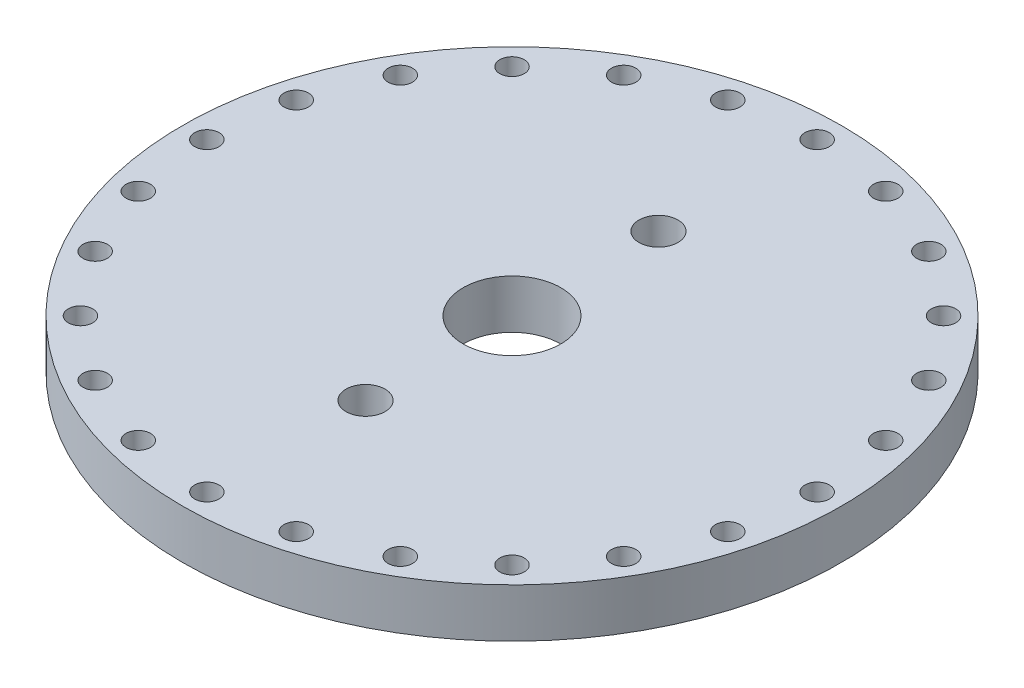
SolidWorks part; units mm, degrees
material "Brass"
ref_plane "Front Plane" through (0, 0, 0) normal (0, 0, 1) x (1, 0, 0)
ref_plane "Top Plane" through (0, 0, 0) normal (0, 1, 0) x (1, 0, 0)
ref_plane "Right Plane" through (0, 0, 0) normal (1, 0, 0) x (0, 0, -1)
sketch "Sketch5" plane through (0, 0, 0) normal (0, 1, 0) x (1, 0, 0)
  line L0 (87.3464, 51.4964) -> (89.0397, 50.8872)
  line L1 (89.0397, 50.8872) -> (90.7249, 50.062)
  line L2 (90.7249, 50.062) -> (90.7249, 49.095)
  line L3 (90.7249, 49.095) -> (89.0397, 48.2698)
  line L4 (89.0397, 48.2698) -> (87.3464, 47.6606)
  line L5 (87.3464, 47.6606) -> (87.2693, 46.4828)
  line L6 (87.2693, 46.4828) -> (88.8685, 45.6578)
  line L7 (88.8685, 45.6578) -> (90.4317, 44.6196)
  line L8 (90.4317, 44.6196) -> (90.3054, 43.6609)
  line L9 (90.3054, 43.6609) -> (88.5268, 43.0627)
  line L10 (88.5268, 43.0627) -> (86.7686, 42.6797)
  line L11 (86.7686, 42.6797) -> (86.5383, 41.5221)
  line L12 (86.5383, 41.5221) -> (88.0162, 40.4955)
  line L13 (88.0162, 40.4955) -> (89.4304, 39.2621)
  line L14 (89.4304, 39.2621) -> (89.1801, 38.328)
  line L15 (89.1801, 38.328) -> (87.3386, 37.9672)
  line L16 (87.3386, 37.9672) -> (85.5454, 37.8169)
  line L17 (85.5454, 37.8169) -> (85.1661, 36.6994)
  line L18 (85.1661, 36.6994) -> (86.4974, 35.4884)
  line L19 (86.4974, 35.4884) -> (87.7385, 34.0811)
  line L20 (87.7385, 34.0811) -> (87.3685, 33.1877)
  line L21 (87.3685, 33.1877) -> (85.4956, 33.0702)
  line L22 (85.4956, 33.0702) -> (83.6981, 33.1553)
  line L23 (83.6981, 33.1553) -> (83.1762, 32.0968)
  line L24 (83.1762, 32.0968) -> (84.3379, 30.7226)
  line L25 (84.3379, 30.7226) -> (85.3848, 29.1653)
  line L26 (85.3848, 29.1653) -> (84.9013, 28.3278)
  line L27 (84.9013, 28.3278) -> (83.0292, 28.4557)
  line L28 (83.0292, 28.4557) -> (81.2581, 28.7747)
  line L29 (81.2581, 28.7747) -> (80.6024, 27.7935)
  line L30 (80.6024, 27.7935) -> (81.575, 26.2794)
  line L31 (81.575, 26.2794) -> (82.4096, 24.5987)
  line L32 (82.4096, 24.5987) -> (81.821, 23.8315)
  line L33 (81.821, 23.8315) -> (79.9815, 24.2028)
  line L34 (79.9815, 24.2028) -> (78.2673, 24.7502)
  line L35 (78.2673, 24.7502) -> (77.4891, 23.8628)
  line L36 (77.4891, 23.8628) -> (78.2556, 22.2348)
  line L37 (78.2556, 22.2348) -> (78.8638, 20.4595)
  line L38 (78.8638, 20.4595) -> (78.18, 19.7757)
  line L39 (78.18, 19.7757) -> (76.4047, 20.3839)
  line L40 (76.4047, 20.3839) -> (74.7767, 21.1504)
  line L41 (74.7767, 21.1504) -> (73.8893, 20.3722)
  line L42 (73.8893, 20.3722) -> (74.4368, 18.658)
  line L43 (74.4368, 18.658) -> (74.808, 16.8186)
  line L44 (74.808, 16.8186) -> (74.0408, 16.2299)
  line L45 (74.0408, 16.2299) -> (72.3602, 17.0645)
  line L46 (72.3602, 17.0645) -> (70.846, 18.0371)
  line L47 (70.846, 18.0371) -> (69.8648, 17.3814)
  line L48 (69.8648, 17.3814) -> (70.1838, 15.6104)
  line L49 (70.1838, 15.6104) -> (70.3117, 13.7382)
  line L50 (70.3117, 13.7382) -> (69.4742, 13.2547)
  line L51 (69.4742, 13.2547) -> (67.9169, 14.3016)
  line L52 (67.9169, 14.3016) -> (66.5427, 15.4634)
  line L53 (66.5427, 15.4634) -> (65.4842, 14.9415)
  line L54 (65.4842, 14.9415) -> (65.5693, 13.1439)
  line L55 (65.5693, 13.1439) -> (65.4518, 11.271)
  line L56 (65.4518, 11.271) -> (64.5584, 10.901)
  line L57 (64.5584, 10.901) -> (63.1511, 12.1422)
  line L58 (63.1511, 12.1422) -> (61.9401, 13.4734)
  line L59 (61.9401, 13.4734) -> (60.8226, 13.0941)
  line L60 (60.8226, 13.0941) -> (60.6724, 11.3009)
  line L61 (60.6724, 11.3009) -> (60.3115, 9.4594)
  line L62 (60.3115, 9.4594) -> (59.3774, 9.2091)
  line L63 (59.3774, 9.2091) -> (58.144, 10.6233)
  line L64 (58.144, 10.6233) -> (57.1174, 12.1012)
  line L65 (57.1174, 12.1012) -> (55.9598, 11.8709)
  line L66 (55.9598, 11.8709) -> (55.5768, 10.1127)
  line L67 (55.5768, 10.1127) -> (54.9786, 8.3341)
  line L68 (54.9786, 8.3341) -> (54.0199, 8.2078)
  line L69 (54.0199, 8.2078) -> (52.9817, 9.771)
  line L70 (52.9817, 9.771) -> (52.1567, 11.3702)
  line L71 (52.1567, 11.3702) -> (50.979, 11.2931)
  line L72 (50.979, 11.2931) -> (50.3698, 9.5998)
  line L73 (50.3698, 9.5998) -> (49.5446, 7.9146)
  line L74 (49.5446, 7.9146) -> (48.5775, 7.9146)
  line L75 (48.5775, 7.9146) -> (47.7523, 9.5998)
  line L76 (47.7523, 9.5998) -> (47.1431, 11.2931)
  line L77 (47.1431, 11.2931) -> (45.9654, 11.3702)
  line L78 (45.9654, 11.3702) -> (45.1403, 9.771)
  line L79 (45.1403, 9.771) -> (44.1021, 8.2078)
  line L80 (44.1021, 8.2078) -> (43.1434, 8.3341)
  line L81 (43.1434, 8.3341) -> (42.5452, 10.1127)
  line L82 (42.5452, 10.1127) -> (42.1622, 11.8709)
  line L83 (42.1622, 11.8709) -> (41.0046, 12.1012)
  line L84 (41.0046, 12.1012) -> (39.978, 10.6233)
  line L85 (39.978, 10.6233) -> (38.7447, 9.2091)
  line L86 (38.7447, 9.2091) -> (37.8106, 9.4594)
  line L87 (37.8106, 9.4594) -> (37.4497, 11.3009)
  line L88 (37.4497, 11.3009) -> (37.2994, 13.0941)
  line L89 (37.2994, 13.0941) -> (36.1819, 13.4734)
  line L90 (36.1819, 13.4734) -> (34.9709, 12.1422)
  line L91 (34.9709, 12.1422) -> (33.5636, 10.901)
  line L92 (33.5636, 10.901) -> (32.6702, 11.271)
  line L93 (32.6702, 11.271) -> (32.5527, 13.1439)
  line L94 (32.5527, 13.1439) -> (32.6378, 14.9415)
  line L95 (32.6378, 14.9415) -> (31.5793, 15.4634)
  line L96 (31.5793, 15.4634) -> (30.2051, 14.3016)
  line L97 (30.2051, 14.3016) -> (28.6478, 13.2547)
  line L98 (28.6478, 13.2547) -> (27.8103, 13.7382)
  line L99 (27.8103, 13.7382) -> (27.9382, 15.6104)
  line L100 (27.9382, 15.6104) -> (28.2572, 17.3814)
  line L101 (28.2572, 17.3814) -> (27.276, 18.0371)
  line L102 (27.276, 18.0371) -> (25.7619, 17.0645)
  line L103 (25.7619, 17.0645) -> (24.0812, 16.2299)
  line L104 (24.0812, 16.2299) -> (23.314, 16.8186)
  line L105 (23.314, 16.8186) -> (23.6853, 18.658)
  line L106 (23.6853, 18.658) -> (24.2327, 20.3722)
  line L107 (24.2327, 20.3722) -> (23.3453, 21.1504)
  line L108 (23.3453, 21.1504) -> (21.7173, 20.3839)
  line L109 (21.7173, 20.3839) -> (19.9421, 19.7757)
  line L110 (19.9421, 19.7757) -> (19.2582, 20.4595)
  line L111 (19.2582, 20.4595) -> (19.8664, 22.2348)
  line L112 (19.8664, 22.2348) -> (20.6329, 23.8628)
  line L113 (20.6329, 23.8628) -> (19.8547, 24.7502)
  line L114 (19.8547, 24.7502) -> (18.1405, 24.2028)
  line L115 (18.1405, 24.2028) -> (16.3011, 23.8315)
  line L116 (16.3011, 23.8315) -> (15.7124, 24.5987)
  line L117 (15.7124, 24.5987) -> (16.547, 26.2794)
  line L118 (16.547, 26.2794) -> (17.5196, 27.7935)
  line L119 (17.5196, 27.7935) -> (16.8639, 28.7747)
  line L120 (16.8639, 28.7747) -> (15.0929, 28.4557)
  line L121 (15.0929, 28.4557) -> (13.2207, 28.3278)
  line L122 (13.2207, 28.3278) -> (12.7372, 29.1653)
  line L123 (12.7372, 29.1653) -> (13.7841, 30.7226)
  line L124 (13.7841, 30.7226) -> (14.9459, 32.0968)
  line L125 (14.9459, 32.0968) -> (14.424, 33.1553)
  line L126 (14.424, 33.1553) -> (12.6264, 33.0702)
  line L127 (12.6264, 33.0702) -> (10.7535, 33.1877)
  line L128 (10.7535, 33.1877) -> (10.3835, 34.0811)
  line L129 (10.3835, 34.0811) -> (11.6247, 35.4884)
  line L130 (11.6247, 35.4884) -> (12.9559, 36.6994)
  line L131 (12.9559, 36.6994) -> (12.5766, 37.8169)
  line L132 (12.5766, 37.8169) -> (10.7834, 37.9672)
  line L133 (10.7834, 37.9672) -> (8.9419, 38.328)
  line L134 (8.9419, 38.328) -> (8.6916, 39.2621)
  line L135 (8.6916, 39.2621) -> (10.1058, 40.4955)
  line L136 (10.1058, 40.4955) -> (11.5837, 41.5221)
  line L137 (11.5837, 41.5221) -> (11.3534, 42.6797)
  line L138 (11.3534, 42.6797) -> (9.5952, 43.0627)
  line L139 (9.5952, 43.0627) -> (7.8167, 43.6609)
  line L140 (7.8167, 43.6609) -> (7.6903, 44.6196)
  line L141 (7.6903, 44.6196) -> (9.2536, 45.6578)
  line L142 (9.2536, 45.6578) -> (10.8528, 46.4828)
  line L143 (10.8528, 46.4828) -> (10.7757, 47.6606)
  line L144 (10.7757, 47.6606) -> (9.0823, 48.2698)
  line L145 (9.0823, 48.2698) -> (7.3971, 49.095)
  line L146 (7.3971, 49.095) -> (7.3971, 50.062)
  line L147 (7.3971, 50.062) -> (9.0823, 50.8872)
  line L148 (9.0823, 50.8872) -> (10.7757, 51.4964)
  line L149 (10.7757, 51.4964) -> (10.8528, 52.6742)
  line L150 (10.8528, 52.6742) -> (9.2536, 53.4992)
  line L151 (9.2536, 53.4992) -> (7.6903, 54.5374)
  line L152 (7.6903, 54.5374) -> (7.8167, 55.4961)
  line L153 (7.8167, 55.4961) -> (9.5952, 56.0943)
  line L154 (9.5952, 56.0943) -> (11.3534, 56.4773)
  line L155 (11.3534, 56.4773) -> (11.5837, 57.6349)
  line L156 (11.5837, 57.6349) -> (10.1058, 58.6615)
  line L157 (10.1058, 58.6615) -> (8.6916, 59.8949)
  line L158 (8.6916, 59.8949) -> (8.9419, 60.829)
  line L159 (8.9419, 60.829) -> (10.7834, 61.1898)
  line L160 (10.7834, 61.1898) -> (12.5766, 61.3401)
  line L161 (12.5766, 61.3401) -> (12.9559, 62.4576)
  line L162 (12.9559, 62.4576) -> (11.6247, 63.6686)
  line L163 (11.6247, 63.6686) -> (10.3835, 65.0759)
  line L164 (10.3835, 65.0759) -> (10.7535, 65.9693)
  line L165 (10.7535, 65.9693) -> (12.6264, 66.0868)
  line L166 (12.6264, 66.0868) -> (14.424, 66.0017)
  line L167 (14.424, 66.0017) -> (14.9459, 67.0602)
  line L168 (14.9459, 67.0602) -> (13.7841, 68.4344)
  line L169 (13.7841, 68.4344) -> (12.7372, 69.9917)
  line L170 (12.7372, 69.9917) -> (13.2207, 70.8292)
  line L171 (13.2207, 70.8292) -> (15.0929, 70.7013)
  line L172 (15.0929, 70.7013) -> (16.8639, 70.3823)
  line L173 (16.8639, 70.3823) -> (17.5196, 71.3635)
  line L174 (17.5196, 71.3635) -> (16.547, 72.8776)
  line L175 (16.547, 72.8776) -> (15.7124, 74.5583)
  line L176 (15.7124, 74.5583) -> (16.3011, 75.3255)
  line L177 (16.3011, 75.3255) -> (18.1405, 74.9542)
  line L178 (18.1405, 74.9542) -> (19.8547, 74.4068)
  line L179 (19.8547, 74.4068) -> (20.6329, 75.2942)
  line L180 (20.6329, 75.2942) -> (19.8664, 76.9222)
  line L181 (19.8664, 76.9222) -> (19.2582, 78.6975)
  line L182 (19.2582, 78.6975) -> (19.9421, 79.3813)
  line L183 (19.9421, 79.3813) -> (21.7173, 78.7731)
  line L184 (21.7173, 78.7731) -> (23.3453, 78.0066)
  line L185 (23.3453, 78.0066) -> (24.2327, 78.7848)
  line L186 (24.2327, 78.7848) -> (23.6853, 80.499)
  line L187 (23.6853, 80.499) -> (23.314, 82.3384)
  line L188 (23.314, 82.3384) -> (24.0812, 82.9271)
  line L189 (24.0812, 82.9271) -> (25.7619, 82.0925)
  line L190 (25.7619, 82.0925) -> (27.276, 81.1199)
  line L191 (27.276, 81.1199) -> (28.2572, 81.7756)
  line L192 (28.2572, 81.7756) -> (27.9382, 83.5466)
  line L193 (27.9382, 83.5466) -> (27.8103, 85.4188)
  line L194 (27.8103, 85.4188) -> (28.6478, 85.9023)
  line L195 (28.6478, 85.9023) -> (30.2051, 84.8554)
  line L196 (30.2051, 84.8554) -> (31.5793, 83.6936)
  line L197 (31.5793, 83.6936) -> (32.6378, 84.2155)
  line L198 (32.6378, 84.2155) -> (32.5527, 86.0131)
  line L199 (32.5527, 86.0131) -> (32.6702, 87.886)
  line L200 (32.6702, 87.886) -> (33.5636, 88.256)
  line L201 (33.5636, 88.256) -> (34.9709, 87.0148)
  line L202 (34.9709, 87.0148) -> (36.1819, 85.6836)
  line L203 (36.1819, 85.6836) -> (37.2994, 86.0629)
  line L204 (37.2994, 86.0629) -> (37.4497, 87.8561)
  line L205 (37.4497, 87.8561) -> (37.8106, 89.6976)
  line L206 (37.8106, 89.6976) -> (38.7447, 89.9479)
  line L207 (38.7447, 89.9479) -> (39.978, 88.5337)
  line L208 (39.978, 88.5337) -> (41.0046, 87.0558)
  line L209 (41.0046, 87.0558) -> (42.1622, 87.2861)
  line L210 (42.1622, 87.2861) -> (42.5452, 89.0443)
  line L211 (42.5452, 89.0443) -> (43.1434, 90.8228)
  line L212 (43.1434, 90.8228) -> (44.1021, 90.9492)
  line L213 (44.1021, 90.9492) -> (45.1403, 89.386)
  line L214 (45.1403, 89.386) -> (45.9654, 87.7868)
  line L215 (45.9654, 87.7868) -> (47.1431, 87.8639)
  line L216 (47.1431, 87.8639) -> (47.7523, 89.5572)
  line L217 (47.7523, 89.5572) -> (48.5775, 91.2424)
  line L218 (48.5775, 91.2424) -> (49.5446, 91.2424)
  line L219 (49.5446, 91.2424) -> (50.3698, 89.5572)
  line L220 (50.3698, 89.5572) -> (50.979, 87.8639)
  line L221 (50.979, 87.8639) -> (52.1567, 87.7868)
  line L222 (52.1567, 87.7868) -> (52.9817, 89.386)
  line L223 (52.9817, 89.386) -> (54.0199, 90.9492)
  line L224 (54.0199, 90.9492) -> (54.9786, 90.8228)
  line L225 (54.9786, 90.8228) -> (55.5768, 89.0443)
  line L226 (55.5768, 89.0443) -> (55.9598, 87.2861)
  line L227 (55.9598, 87.2861) -> (57.1174, 87.0558)
  line L228 (57.1174, 87.0558) -> (58.144, 88.5337)
  line L229 (58.144, 88.5337) -> (59.3774, 89.9479)
  line L230 (59.3774, 89.9479) -> (60.3115, 89.6976)
  line L231 (60.3115, 89.6976) -> (60.6724, 87.8561)
  line L232 (60.6724, 87.8561) -> (60.8226, 86.0629)
  line L233 (60.8226, 86.0629) -> (61.9401, 85.6836)
  line L234 (61.9401, 85.6836) -> (63.1511, 87.0148)
  line L235 (63.1511, 87.0148) -> (64.5584, 88.256)
  line L236 (64.5584, 88.256) -> (65.4518, 87.886)
  line L237 (65.4518, 87.886) -> (65.5693, 86.0131)
  line L238 (65.5693, 86.0131) -> (65.4842, 84.2155)
  line L239 (65.4842, 84.2155) -> (66.5427, 83.6936)
  line L240 (66.5427, 83.6936) -> (67.9169, 84.8554)
  line L241 (67.9169, 84.8554) -> (69.4742, 85.9023)
  line L242 (69.4742, 85.9023) -> (70.3117, 85.4188)
  line L243 (70.3117, 85.4188) -> (70.1838, 83.5466)
  line L244 (70.1838, 83.5466) -> (69.8648, 81.7756)
  line L245 (69.8648, 81.7756) -> (70.846, 81.1199)
  line L246 (70.846, 81.1199) -> (72.3602, 82.0925)
  line L247 (72.3602, 82.0925) -> (74.0408, 82.9271)
  line L248 (74.0408, 82.9271) -> (74.808, 82.3384)
  line L249 (74.808, 82.3384) -> (74.4368, 80.499)
  line L250 (74.4368, 80.499) -> (73.8893, 78.7848)
  line L251 (73.8893, 78.7848) -> (74.7767, 78.0066)
  line L252 (74.7767, 78.0066) -> (76.4047, 78.7731)
  line L253 (76.4047, 78.7731) -> (78.18, 79.3813)
  line L254 (78.18, 79.3813) -> (78.8638, 78.6975)
  line L255 (78.8638, 78.6975) -> (78.2556, 76.9222)
  line L256 (78.2556, 76.9222) -> (77.4891, 75.2942)
  line L257 (77.4891, 75.2942) -> (78.2673, 74.4068)
  line L258 (78.2673, 74.4068) -> (79.9815, 74.9542)
  line L259 (79.9815, 74.9542) -> (81.821, 75.3255)
  line L260 (81.821, 75.3255) -> (82.4096, 74.5583)
  line L261 (82.4096, 74.5583) -> (81.575, 72.8776)
  line L262 (81.575, 72.8776) -> (80.6024, 71.3635)
  line L263 (80.6024, 71.3635) -> (81.2581, 70.3823)
  line L264 (81.2581, 70.3823) -> (83.0292, 70.7013)
  line L265 (83.0292, 70.7013) -> (84.9013, 70.8292)
  line L266 (84.9013, 70.8292) -> (85.3848, 69.9917)
  line L267 (85.3848, 69.9917) -> (84.3379, 68.4344)
  line L268 (84.3379, 68.4344) -> (83.1762, 67.0602)
  line L269 (83.1762, 67.0602) -> (83.6981, 66.0017)
  line L270 (83.6981, 66.0017) -> (85.4956, 66.0868)
  line L271 (85.4956, 66.0868) -> (87.3685, 65.9693)
  line L272 (87.3685, 65.9693) -> (87.7385, 65.0759)
  line L273 (87.7385, 65.0759) -> (86.4974, 63.6686)
  line L274 (86.4974, 63.6686) -> (85.1661, 62.4576)
  line L275 (85.1661, 62.4576) -> (85.5454, 61.3401)
  line L276 (85.5454, 61.3401) -> (87.3386, 61.1898)
  line L277 (87.3386, 61.1898) -> (89.1801, 60.829)
  line L278 (89.1801, 60.829) -> (89.4304, 59.8949)
  line L279 (89.4304, 59.8949) -> (88.0162, 58.6615)
  line L280 (88.0162, 58.6615) -> (86.5383, 57.6349)
  line L281 (86.5383, 57.6349) -> (86.7686, 56.4773)
  line L282 (86.7686, 56.4773) -> (88.5268, 56.0943)
  line L283 (88.5268, 56.0943) -> (90.3054, 55.4961)
  line L284 (90.3054, 55.4961) -> (90.4317, 54.5374)
  line L285 (90.4317, 54.5374) -> (88.8685, 53.4992)
  line L286 (88.8685, 53.4992) -> (87.2693, 52.6742)
  line L287 (87.2693, 52.6742) -> (87.3464, 51.4964)
  line L288 (49.061, 91.2424) -> (49.061, 7.9146) construction
  line L289 (7.3971, 49.5785) -> (90.7249, 49.5785) construction
  point P292 (49.061, 49.5785)
sketch "Sketch6" plane through (0, 0, 0) normal (0, 1, 0) x (1, 0, 0)
  line L0 (49.061, 91.2424) -> (49.061, 7.9146) construction
  circle A0 centre (49.061, 49.5785) radius 4
  dimension "D1" = 8
sketch "Sketch7" plane through (0, 0, 0) normal (0, 1, 0) x (1, 0, 0)
  line L0 (49.061, 91.2424) -> (49.061, 7.9146) construction
  line L1 (25.4921, 49.5785) -> (64.6594, 49.5785) construction
  line L2 (7.3971, 49.5785) -> (90.7249, 49.5785) construction
  circle A0 centre (49.061, 61.5785) radius 1.6
  circle A1 centre (49.061, 37.5785) radius 1.6
  dimension "D2" = 3.2
  dimension "D1" = 12
sketch "Sketch8" plane through (0, 0, 0) normal (0, 1, 0) x (1, 0, 0)
  line L0 (7.3971, 49.5785) -> (90.7249, 49.5785) construction
  circle A0 centre (49.061, 49.5785) radius 27
  dimension "D1" = 54
sketch "Sketch9" plane through (0, 0, 0) normal (0, 1, 0) x (1, 0, 0)
  line L0 (49.061, 91.2424) -> (49.061, 7.9146) construction
  line L1 (49.061, 74.5785) -> (49.061, 76.5785) construction
  circle A0 centre (49.061, 74.5785) radius 1
  circle A1 centre (49.061, 49.5785) radius 27 construction
  circle A2 centre (55.5315, 73.7266) radius 1
  circle A3 centre (61.561, 71.2291) radius 1
  circle A4 centre (66.7387, 67.2562) radius 1
  circle A5 centre (70.7116, 62.0785) radius 1
  circle A6 centre (73.2092, 56.049) radius 1
  circle A7 centre (74.061, 49.5785) radius 1
  circle A8 centre (73.2092, 43.108) radius 1
  circle A9 centre (70.7116, 37.0785) radius 1
  circle A10 centre (66.7387, 31.9008) radius 1
  circle A11 centre (61.561, 27.9279) radius 1
  circle A12 centre (55.5315, 25.4304) radius 1
  circle A13 centre (49.061, 24.5785) radius 1
  circle A14 centre (42.5905, 25.4304) radius 1
  circle A15 centre (36.561, 27.9279) radius 1
  circle A16 centre (31.3833, 31.9008) radius 1
  circle A17 centre (27.4104, 37.0785) radius 1
  circle A18 centre (24.9129, 43.108) radius 1
  circle A19 centre (24.061, 49.5785) radius 1
  circle A20 centre (24.9129, 56.049) radius 1
  circle A21 centre (27.4104, 62.0785) radius 1
  circle A22 centre (31.3833, 67.2562) radius 1
  circle A23 centre (36.561, 71.2291) radius 1
  circle A24 centre (42.5905, 73.7266) radius 1
  point P55 (49.061, 49.5785)
  dimension "D1" = 2
  dimension "D2" = 2
  dimension "D3" = 24
extrude "Boss-Extrude1" add sketch "Sketch8" along normal blind 4
extrude "Boss-Extrude2" [suppressed] add sketch "Sketch5" along normal up to surface (4 mm away) up to face at (49.061, 4, -22.5785)
extrude "Cut-Extrude1" cut sketch "Sketch6" along normal up to next
extrude "Cut-Extrude2" cut sketch "Sketch7" along normal up to next
extrude "Cut-Extrude3" cut sketch "Sketch9" along normal up to next
ref_axis "Axis1" [suppressed] through (49.061, 4, -49.5785) along (0, -1, 0)
